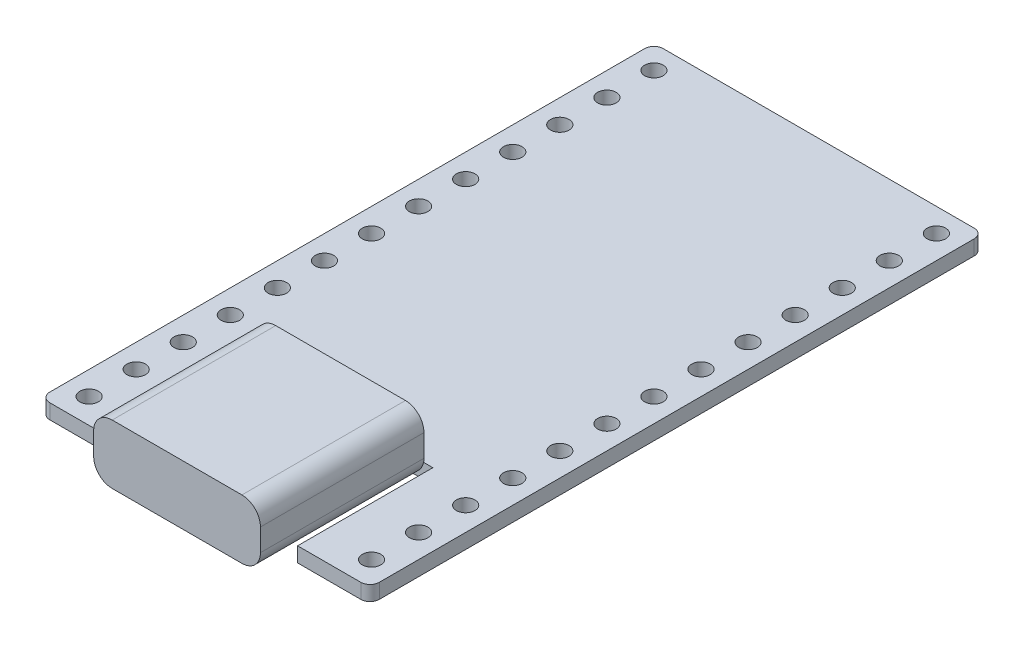
SolidWorks part; units mm, degrees
ref_plane "Front Plane" through (0, 0, 0) normal (0, 0, 1) x (1, 0, 0)
ref_plane "Top Plane" through (0, 0, 0) normal (0, 1, 0) x (1, 0, 0)
ref_plane "Right Plane" through (0, 0, 0) normal (1, 0, 0) x (0, 0, -1)
sketch "Sketch1" plane through (0, 0, 0) normal (0, 1, 0) x (1, 0, 0)
  line L0 (-8.89, 16.55) -> (8.89, -16.55) construction
  line L1 (-8.89, 16.55) -> (8.89, 16.55)
  line L2 (-8.89, 16.55) -> (-8.89, -16.55)
  line L3 (-8.89, -16.55) -> (8.89, -16.55)
  line L4 (8.89, 16.55) -> (8.89, -16.55)
  line L5 (8.89, 16.55) -> (-8.89, -16.55) construction
  point P4 (0, 0)
  point P12 (0, 0)
  dimension "D1" = 17.78
  dimension "D2" = 33.1
extrude "Boss-Extrude1" add sketch "Sketch1" along normal blind 0.8
fillet "Fillet1" radius 0.5 4 edges at (8.89, 0.4, 16.55) (-8.89, 0.4, 16.55) (-8.89, 0.4, -16.55) (8.89, 0.4, -16.55)
sketch "Sketch2" plane through (0, 0.8, 0) normal (0, 1, 0) x (1, 0, 0)
  line L1 (4.5, -16.55) -> (-4.5, -16.55)
  line L2 (4.5, -16.55) -> (4.5, -9.25)
  line L3 (4.5, -9.25) -> (-4.5, -9.25)
  line L4 (-8.39, -16.55) -> (8.39, -16.55)
  line L5 (8.89, -16.05) -> (8.89, 16.05)
  line L6 (8.39, 16.55) -> (-8.39, 16.55)
  line L7 (-8.89, 16.05) -> (-8.89, -16.05)
  line L8 (-8.39, -16.55) -> (8.39, -16.55)
  line L9 (8.89, -16.05) -> (8.89, 16.05)
  line L10 (8.39, 16.55) -> (-8.39, 16.55)
  line L11 (-8.89, 16.05) -> (-8.89, -16.05)
  line L12 (-4.5, -16.55) -> (-4.5, -9.25)
  arc A4 (8.39, -16.55) -> (8.89, -16.05) centre (8.39, -16.05) ccw
  arc A5 (8.89, 16.05) -> (8.39, 16.55) centre (8.39, 16.05) ccw
  arc A6 (-8.39, 16.55) -> (-8.89, 16.05) centre (-8.39, 16.05) ccw
  arc A7 (-8.89, -16.05) -> (-8.39, -16.55) centre (-8.39, -16.05) ccw
  arc A8 (8.39, -16.55) -> (8.89, -16.05) centre (8.39, -16.05) ccw
  arc A9 (8.89, 16.05) -> (8.39, 16.55) centre (8.39, 16.05) ccw
  arc A10 (-8.39, 16.55) -> (-8.89, 16.05) centre (-8.39, 16.05) ccw
  arc A11 (-8.89, -16.05) -> (-8.39, -16.55) centre (-8.39, -16.05) ccw
  point P15 (0, -16.55)
  point P17 (0, -16.55)
  line M13 (-8.39, -16.55) -> (8.39, -16.55)
  dimension "D2" = 9
  dimension "D3" = 7.3
  dimension "D1" = 0
extrude "Cut-Extrude1" cut sketch "Sketch2" against normal blind 0.8 contours L12 L2 L3 M13 region at (0, 0.8, 12.9)
extrude "Boss-Extrude2" add sketch "Sketch2<3>" along normal blind 2.4 separate body contours L1 L12 L3 L2
sketch "Sketch2<3>" plane through (0, 0.8, 0) normal (0, 1, 0) x (1, 0, 0) same geometry as "Sketch2"
sketch "Sketch4" plane through (0, 0, 16.55) normal (0, 0, 1) x (1, 0, 0)
  line L4 (-4.5, 0.8) -> (4.5, 0.8)
  line L5 (4.5, 0.8) -> (4.5, 3.2)
  line L6 (4.5, 3.2) -> (-4.5, 3.2)
  line L7 (-4.5, 3.2) -> (-4.5, 0.8)
  line L8 (-4.5, 0.8) -> (4.5, 0.8)
  line L9 (4.5, 0.8) -> (4.5, 3.2)
  line L10 (4.5, 3.2) -> (-4.5, 3.2)
  line L11 (-4.5, 3.2) -> (-4.5, 0.8)
  dimension "D1" = 0
extrude "Boss-Extrude3" add sketch "Sketch4" along normal blind 1.524
sketch "Sketch5" plane through (0, 0.8, 0) normal (0, -1, 0) x (1, 0, 0)
  line L4 (4.5, 9.25) -> (4.5, 18.074)
  line L5 (4.5, 18.074) -> (-4.5, 18.074)
  line L6 (-4.5, 18.074) -> (-4.5, 9.25)
  line L7 (-4.5, 9.25) -> (4.5, 9.25)
  line L8 (4.5, 9.25) -> (4.5, 18.074)
  line L9 (4.5, 18.074) -> (-4.5, 18.074)
  line L10 (-4.5, 18.074) -> (-4.5, 9.25)
  line L11 (-4.5, 9.25) -> (4.5, 9.25)
  dimension "D1" = 0
extrude "Boss-Extrude4" add sketch "Sketch5" along normal up to surface (0.8 mm away) up to face at (0, 0, 4.3)
sketch "Sketch6" plane through (0, 0.8, 0) normal (0, 1, 0) x (1, 0, 0)
  line L0 (8.39, 16.55) -> (-8.39, 16.55) construction
  line L1 (-7.62, 15.28) -> (7.62, 15.28) construction
  line L2 (-8.89, 16.05) -> (-8.89, -16.05) construction
  line L3 (-7.62, 15.28) -> (-7.62, 12.74) construction
  circle A0 centre (-7.62, 15.28) radius 0.5
  circle A26 centre (7.62, 15.28) radius 0.5
  circle A27 centre (7.62, 12.74) radius 0.5
  circle A28 centre (7.62, 10.2) radius 0.5
  circle A29 centre (7.62, 7.66) radius 0.5
  circle A30 centre (7.62, 5.12) radius 0.5
  circle A31 centre (7.62, 2.58) radius 0.5
  circle A32 centre (7.62, 0.04) radius 0.5
  circle A33 centre (7.62, -2.5) radius 0.5
  circle A34 centre (7.62, -5.04) radius 0.5
  circle A35 centre (7.62, -7.58) radius 0.5
  circle A36 centre (7.62, -10.12) radius 0.5
  circle A37 centre (7.62, -12.66) radius 0.5
  circle A38 centre (7.62, -15.2) radius 0.5
  circle A39 centre (-7.62, 12.74) radius 0.5
  circle A40 centre (-7.62, 10.2) radius 0.5
  circle A41 centre (-7.62, 7.66) radius 0.5
  circle A42 centre (-7.62, 5.12) radius 0.5
  circle A43 centre (-7.62, 2.58) radius 0.5
  circle A44 centre (-7.62, 0.04) radius 0.5
  circle A45 centre (-7.62, -2.5) radius 0.5
  circle A46 centre (-7.62, -5.04) radius 0.5
  circle A47 centre (-7.62, -7.58) radius 0.5
  circle A48 centre (-7.62, -10.12) radius 0.5
  circle A49 centre (-7.62, -12.66) radius 0.5
  circle A50 centre (-7.62, -15.2) radius 0.5
  dimension "D1" = 1
  dimension "D2" = 1.27
  dimension "D3" = 1.27
  dimension "D6" = 15.24
  dimension "D7" = 2.54
  dimension "D4" = 2
  dimension "D5" = 13
extrude "Cut-Extrude2" cut sketch "Sketch6" against normal blind 1.524
fillet "Fillet2" radius 1 4 edges at (-4.5, 3.2, 13.662) (4.5, 3.2, 13.662) (4.5, 0, 17.312) (-4.5, 0, 17.312)
sketch "Sketch7" plane through (0, 0, 16.55) normal (0, 0, 1) x (1, 0, 0)
  line L14 (-8.39, 0) -> (-3.5, 0) construction
  line L15 (-4.4798, 0.8) -> (-8.39, 0.8) construction
  line L16 (-8.39, 0.8) -> (-8.39, 0) construction
  line L17 (8.39, 0.8) -> (4.4798, 0.8) construction
  line L18 (3.5, 0) -> (8.39, 0) construction
  line L19 (8.39, 0) -> (8.39, 0.8) construction
  line L20 (-8.39, 0) -> (-3.5, 0)
  line L21 (-4.4798, 0.8) -> (-8.39, 0.8)
  line L22 (-8.39, 0.8) -> (-8.39, 0)
  line L23 (8.39, 0.8) -> (4.4798, 0.8)
  line L24 (3.5, 0) -> (8.39, 0)
  line L25 (8.39, 0) -> (8.39, 0.8)
  line L26 (-4.9798, 0.8) -> (-4.9798, 0)
  line L27 (4.9798, 0.8) -> (4.9798, 0)
  arc A4 (-4.4798, 0.8) -> (-3.5, 0) centre (-3.5, 1) ccw construction
  arc A5 (3.5, 0) -> (4.4798, 0.8) centre (3.5, 1) ccw construction
  arc A6 (-4.4798, 0.8) -> (-3.5, 0) centre (-3.5, 1) ccw
  arc A7 (3.5, 0) -> (4.4798, 0.8) centre (3.5, 1) ccw
  arc M10 (-3.5, 0) -> (-4.4798, 0.8) centre (-3.5, 1) cw
  line M11 (-4.4798, 0.8) -> (-8.39, 0.8)
  dimension "D1" = 0.5
  dimension "D2" = 0.5
extrude "Cut-Extrude5" cut sketch "Sketch7" against normal up to surface (7.3 mm away) contours A7 L24 L27 L23 | L26 L20 M11 M10 region at (-4.5739, 0.3355, 16.55) region at (4.5739, 0.3355, 16.55) up to face at (0, 1.8516, 9.25)
